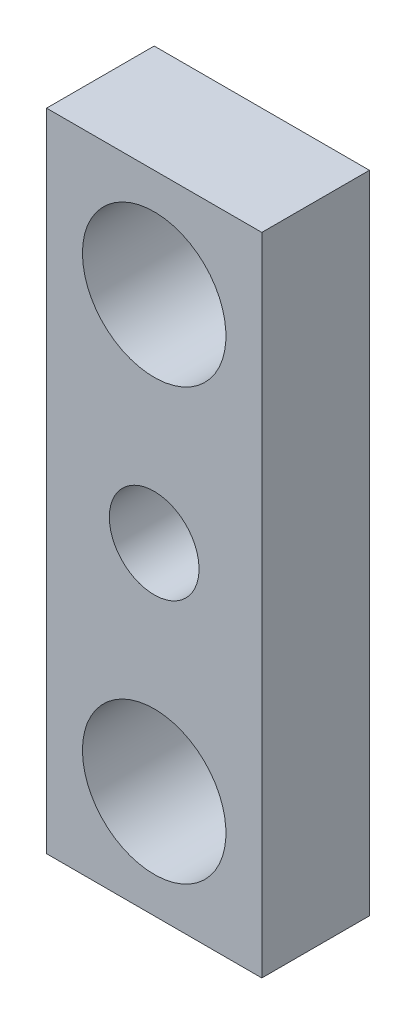
SolidWorks part; units mm, degrees
material "2024-T4"
ref_plane "Front Plane" through (0, 0, 0) normal (0, 0, 1) x (1, 0, 0)
ref_plane "Top Plane" through (0, 0, 0) normal (0, 1, 0) x (1, 0, 0)
ref_plane "Right Plane" through (0, 0, 0) normal (1, 0, 0) x (0, 0, -1)
sketch "Sketch1" plane through (0, 0, 0) normal (0, 0, 1) x (1, 0, 0)
  line L0 (0, -180.975) -> (0, -219.075) construction
  line L1 (0, -200.025) -> (-9.525, -200.025) construction
  line L2 (-9.525, -228.6) -> (9.525, -228.6)
  line L3 (-9.525, -228.6) -> (-9.525, -171.45)
  line L4 (-9.525, -171.45) -> (9.525, -171.45)
  line L5 (9.525, -228.6) -> (9.525, -171.45)
  line L6 (-9.525, -228.6) -> (9.525, -171.45) construction
  line L7 (-9.525, -171.45) -> (9.525, -228.6) construction
  circle A0 centre (0, -180.975) radius 3.175 construction
  circle A1 centre (0, -200.025) radius 3.9687
  circle A2 centre (0, -180.975) radius 6.35
  circle A3 centre (0, -219.075) radius 3.175 construction
  circle A4 centre (0, -219.075) radius 6.35
  dimension "D1" = 6.35
  dimension "D2" = 7.9375
  dimension "D3" = 19.05
  dimension "D6" = 12.7
  dimension "D4" = 19.05
  dimension "D5" = 57.15
extrude "Boss-Extrude2" add sketch "Sketch1" along normal blind 9.525
